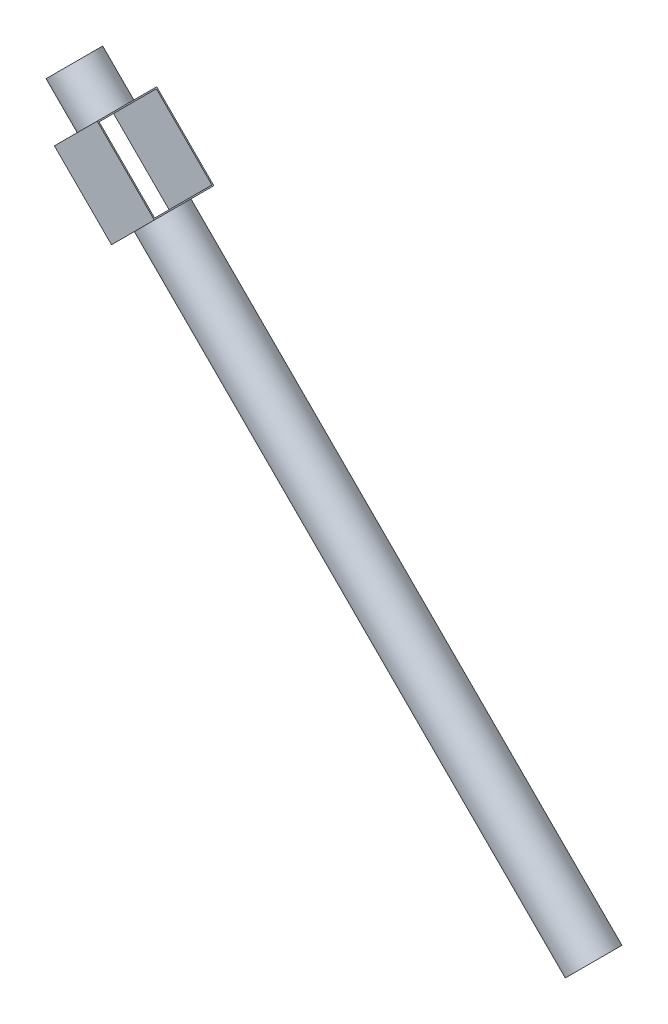
SolidWorks part; units mm, degrees
other "Marca1"
sketch "Croquis24" plane through (155.1349, 1458.7613, 53.4337) normal (0.1681, 0.8135, 0.5568) x (0.9841, -0.1718, -0.0461)
other "Marca2"
sketch "Croquis25" plane through (-1370.0944, 1458.7613, 53.4337) normal (-0.0644, 0.9432, 0.3258) x (0.9966, 0.0774, -0.027)
material "AISI 316 Chapa de acero inoxidable (SS)"
ref_plane "Alzado" through (0, 0, 0) normal (0, 0, 1) x (1, 0, 0)
ref_plane "Planta" through (0, 0, 0) normal (0, 1, 0) x (1, 0, 0)
ref_plane "Vista lateral" through (0, 0, 0) normal (1, 0, 0) x (0, 0, -1)
sketch3d "Croquis3D1"
  line L0 (0, 0, 0) -> (88.6669, 0, 0) construction
  line L1 (88.6669, 0, 0) -> (88.6669, 0, -55.1326) construction
ref_plane "Plano1" through (44.3335, 44.3335, 0) normal (0.7071, 0.7071, 0) x (0, 0, -1)
ref_plane "Plano2" through (44.3335, -44.3335, 0) normal (0.7071, -0.7071, 0) x (0, 0, -1)
sketch "Croquis1" plane through (44.3335, -44.3335, 0) normal (0.7071, -0.7071, 0) x (0, 0, -1)
  line L0 (0, 62.697) -> (55.1326, 62.697) construction
  circle A0 centre (27.5663, 62.697) radius 63
  circle A1 centre (27.5663, 62.697) radius 60
  dimension "D1" = 126
  dimension "D2" = 120
extrude "Saliente-Extruir1" add sketch "Croquis1" against normal blind 2000
sketch "Croquis3" plane through (44.3335, 44.3335, 0) normal (0.7071, 0.7071, 0) x (0, 0, -1)
  line L0 (-35.4337, 1937.303) -> (-35.4337, 1817.303)
  line L1 (-35.4337, 1937.303) -> (-35.4337, -62.697) construction
  line L3 (-53.4337, 1817.303) -> (108.5663, 1817.303)
  line L4 (-53.4337, 1817.303) -> (-53.4337, 1597.303)
  line L5 (-53.4337, 1597.303) -> (108.5663, 1597.303)
  line L6 (108.5663, 1817.303) -> (108.5663, 1597.303)
  line L7 (27.5663, 1817.303) -> (27.5663, 1597.303) construction
  line L8 (27.5663, 1937.303) -> (27.5663, -62.697) construction
  dimension "D1" = 120
  dimension "D2" = 162
  dimension "D3" = 220
extrude "Saliente-Extruir2" add sketch "Croquis3" along normal mid plane 165 contours L4 L3 L6 L5
sketch "Croquis5" plane through (102.6698, 102.6698, 0) normal (0.7071, 0.7071, 0) x (0, 0, -1)
  line L8 (-50.4337, 1600.303) -> (105.5663, 1600.303)
  line L9 (105.5663, 1600.303) -> (105.5663, 1814.303)
  line L10 (105.5663, 1814.303) -> (-50.4337, 1814.303)
  line L11 (-50.4337, 1814.303) -> (-50.4337, 1600.303)
  line L12 (-50.4337, 1600.303) -> (105.5663, 1600.303)
  line L13 (105.5663, 1600.303) -> (105.5663, 1814.303)
  line L14 (105.5663, 1814.303) -> (-50.4337, 1814.303)
  line L15 (-50.4337, 1814.303) -> (-50.4337, 1600.303)
  dimension "D1" = 3
extrude "Cortar-Extruir1" cut sketch "Croquis5" against normal blind 165
